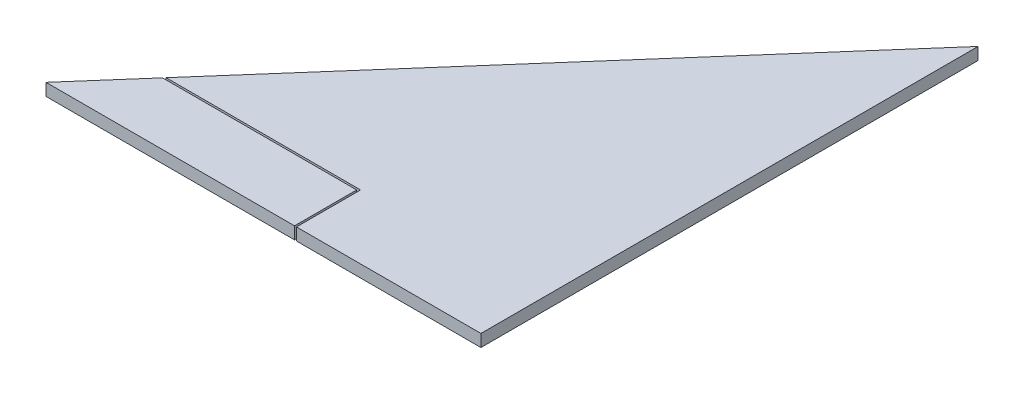
SolidWorks part; units mm, degrees
ref_plane "Front Plane" through (0, 0, 0) normal (0, 0, 1) x (1, 0, 0)
ref_plane "Top Plane" through (0, 0, 0) normal (0, 1, 0) x (1, 0, 0)
ref_plane "Right Plane" through (0, 0, 0) normal (1, 0, 0) x (0, 0, -1)
sketch "Sketch1" plane through (0, 0, 0) normal (0, 1, 0) x (1, 0, 0)
  line L0 (0, 0) -> (0, 203.2)
  line L1 (0, 203.2) -> (-177.8, 0)
  line L2 (-177.8, 0) -> (0, 0)
  line L3 (-76.2, 0) -> (-76.2, 25.4)
  line L4 (-76.2, 25.4) -> (-155.575, 25.4)
  dimension "D1" = 203.2
  dimension "D2" = 177.8
  dimension "D3" = 101.6
  dimension "D4" = 25.4
extrude "Boss-Extrude1" add sketch "Sketch1" along normal blind 5 contours L4 L3 L2 L0 L1 | L3 L4 L1 L2 region at (-50.1693, 0, -75.8319) region at (-121.6712, 0, -12.1801)
extrude "Cut-Extrude-Thin1" cut sketch "Sketch1<3>" along normal blind 6 thin contours L3 L4 thin type one direction wall 0.7937
sketch "Sketch1<3>" plane through (0, 0, 0) normal (0, 1, 0) x (1, 0, 0) same geometry as "Sketch1"
